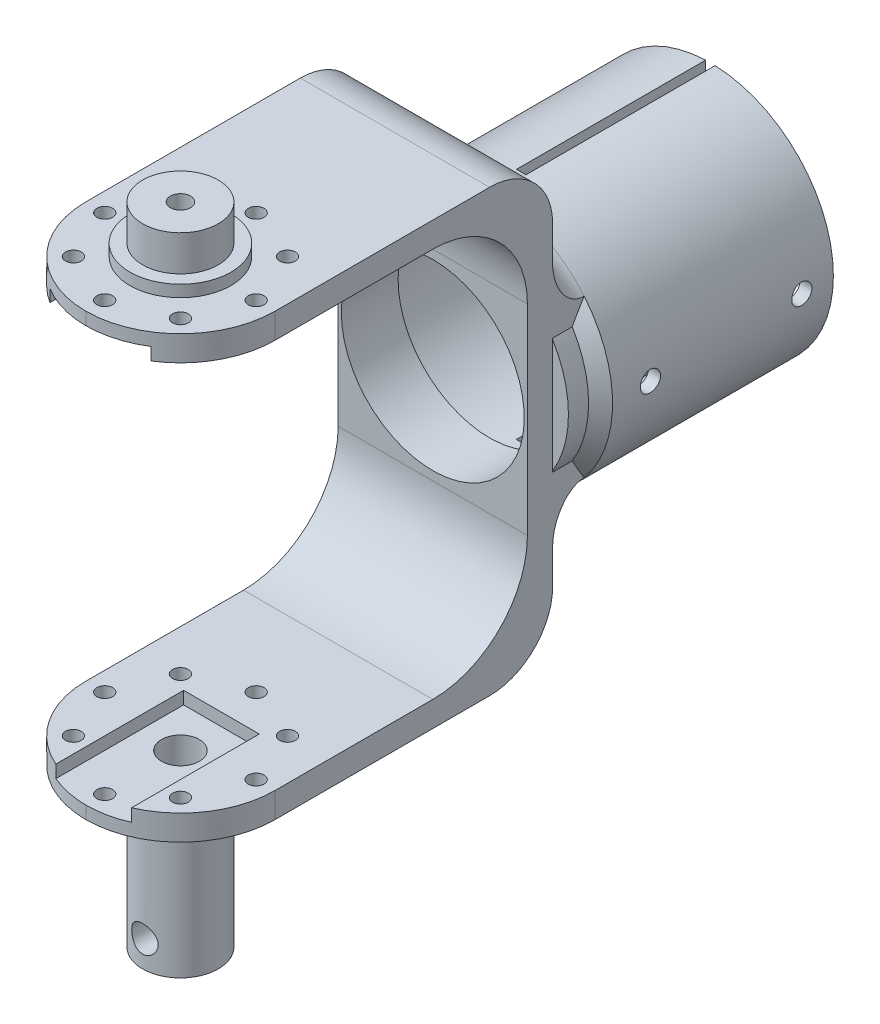
SolidWorks part; units mm, degrees
ref_plane "前视基准面" through (0, 0, 0) normal (0, 0, 1) x (1, 0, 0)
ref_plane "上视基准面" through (0, 0, 0) normal (0, 1, 0) x (1, 0, 0)
ref_plane "右视基准面" through (0, 0, 0) normal (1, 0, 0) x (0, 0, -1)
sketch "草图1" plane through (0, 0, 0) normal (1, 0, 0) x (0, 0, -1)
  line L0 (-27.5, 34.9) -> (31.5, 34.9)
  line L1 (-27.5, 30.9) -> (27.5, 30.9)
  line L2 (31.5, 34.9) -> (31.5, -34.9)
  line L3 (-27.5, -30.9) -> (27.5, -30.9)
  line L4 (27.5, 30.9) -> (27.5, -30.9)
  line L5 (-27.5, 30.9) -> (27.5, -30.9) construction
  line L6 (-27.5, -30.9) -> (27.5, 30.9) construction
  line L7 (-27.5, -34.9) -> (31.5, -34.9)
  line L8 (-27.5, 34.9) -> (-27.5, 30.9)
  line L9 (-27.5, -30.9) -> (-27.5, -34.9)
  point P0 (0, 0)
  dimension "D1" = 61.8
  dimension "D2" = 55
  dimension "D4" = 55
  dimension "D3" = 4
extrude "凸台-拉伸1" add sketch "草图1" along normal blind 30
sketch "草图4" plane through (0, 34.9, 0) normal (0, 1, 0) x (1, 0, 0)
  line L0 (30, 31.5) -> (30, -27.5) construction
  line L1 (30, -27.5) -> (0, -27.5) construction
  circle A0 centre (15, -12.5) radius 12 construction
  circle A1 centre (15, -0.5) radius 1.25
  circle A2 centre (15, -12.5) radius 12 construction
  circle A3 centre (23.4853, -4.0147) radius 1.25
  circle A4 centre (15, -12.5) radius 12 construction
  circle A5 centre (27, -12.5) radius 1.25
  circle A6 centre (15, -12.5) radius 12 construction
  circle A7 centre (23.4853, -20.9853) radius 1.25
  circle A8 centre (15, -12.5) radius 12 construction
  circle A9 centre (15, -24.5) radius 1.25
  circle A10 centre (15, -12.5) radius 12 construction
  circle A11 centre (6.5147, -20.9853) radius 1.25
  circle A12 centre (15, -12.5) radius 12 construction
  circle A13 centre (3, -12.5) radius 1.25
  circle A14 centre (15, -12.5) radius 12 construction
  circle A15 centre (6.5147, -4.0147) radius 1.25
  circle A16 centre (15, -12.5) radius 1.6
  point P31 (15, -12.5)
  dimension "D2" = 15
  dimension "D3" = 24
  dimension "D4" = 2.5
  dimension "D6" = 3.2
  dimension "D1" = 15
  dimension "D5" = 8
extrude "切除-拉伸1" cut sketch "草图4" against normal through all
fillet "圆角1" radius 15 6 edges at (0, 32.9, 27.5) (30, 32.9, 27.5) (30, -32.9, 27.5) (0, -32.9, 27.5) (15, -30.9, -27.5) (15, 30.9, -27.5)
fillet "圆角2" radius 10 2 edges at (15, -34.9, -31.5) (15, 34.9, -31.5)
sketch "草图5" plane through (0, 0, -31.5) normal (0, 0, -1) x (-1, 0, 0)
  line L0 (-30, -24.9) -> (-30, 24.9) construction
  circle A0 centre (-15, 0) radius 17.6
  circle A1 centre (-15, 0) radius 19.5
  dimension "D2" = 35.2
  dimension "D3" = 39
  dimension "D1" = 15
extrude "凸台-拉伸2" add sketch "草图5" along normal blind 40
sketch "草图7" plane through (0, 0, -71.5) normal (0, 0, -1) x (-1, 0, 0)
  line L1 (-15.75, 42.3131) -> (-14.25, 42.3131)
  line L2 (-15.75, 42.3131) -> (-15.75, -42.3131)
  line L3 (-15.75, -42.3131) -> (-14.25, -42.3131)
  line L4 (-14.25, 42.3131) -> (-14.25, -42.3131)
  line L5 (-15.75, 42.3131) -> (-14.25, -42.3131) construction
  line L6 (-15.75, -42.3131) -> (-14.25, 42.3131) construction
  point P0 (-15, 0)
  dimension "D1" = 1.5
extrude "切除-拉伸3" cut sketch "草图7" against normal blind 30
sketch "草图8" plane through (0, 0, 0) normal (1, 0, 0) x (0, 0, -1)
  line L0 (-977.5, 0) -> (49022.5, 0) construction
  line L1 (27.5, 15.9) -> (27.5, -15.9) construction
  line L2 (71.5, -19.4856) -> (71.5, 19.4856) construction
  line L3 (27.5, 15.9) -> (27.5, -15.9) construction
  circle A0 centre (66.5, 0) radius 1.6
  circle A1 centre (42.5, 0) radius 1.6
  point P5 (27.5, 0)
  dimension "D1" = 3.2
  dimension "D2" = 15
  dimension "D3" = 5
  dimension "D4" = 3.2
extrude "切除-拉伸4" cut sketch "草图8" along normal through all and the other way blind 8
sketch "草图10" plane through (0, 0, -31.5) normal (0, 0, -1) x (-1, 0, 0)
  circle A0 centre (-15, 0) radius 17.5
extrude "凸台-拉伸4" add sketch "草图10" along normal blind 5
chamfer "倒角2" distance 5 angle 45 2 edges at (34.5, 0, -31.5) (-4.5, 0, -31.5)
sketch "草图11" plane through (0, -34.9, 0) normal (0, -1, 0) x (1, 0, 0)
  circle A0 centre (15, 12.5) radius 8
  circle A1 centre (15, 12.5) radius 3
  dimension "D1" = 16
  dimension "D2" = 6
extrude "凸台-拉伸5" add sketch "草图11" along normal blind 25
sketch "草图12" plane through (0, -59.9, 0) normal (0, -1, 0) x (1, 0, 0)
  circle A0 centre (15, 12.5) radius 6
  dimension "D1" = 12
extrude "切除-拉伸5" cut sketch "草图12" against normal blind 23.15 flip side to cut
sketch "草图15" plane through (0, 34.9, 0) normal (0, 1, 0) x (1, 0, 0)
  circle A0 centre (15, -12.5) radius 8
  circle A1 centre (15, -12.5) radius 1.6
  dimension "D1" = 16
  dimension "D2" = 3.2
extrude "凸台-拉伸6" add sketch "草图15" along normal blind 7.5
sketch "草图16" plane through (0, 42.4, 0) normal (0, 1, 0) x (1, 0, 0)
  circle A0 centre (15, -12.5) radius 6
  dimension "D1" = 12
extrude "切除-拉伸6" cut sketch "草图16" against normal blind 5.65 flip side to cut
fillet "圆角3" radius 5 2 edges at (15, 19.5, -31.5) (15, -19.5, -31.5)
sketch "草图17" plane through (0, -34.9, 0) normal (0, -1, 0) x (1, 0, 0)
  circle A0 centre (15, 12.5) radius 3 construction
  circle A1 centre (15, 12.5) radius 3
extrude "切除-拉伸7" cut sketch "草图17" against normal blind 8
ref_plane "基准面1" through (0, 0, 12.5) normal (0, 0, -1) x (-1, 0, 0)
sketch "草图19" plane through (0, 0, 12.5) normal (0, 0, -1) x (-1, 0, 0)
  line L0 (0, 30.9) -> (-30, 30.9) construction
  line L1 (-7, 32.9) -> (-23, 32.9)
  line L2 (-7, 32.9) -> (-7, 28.9)
  line L3 (-7, 28.9) -> (-23, 28.9)
  line L4 (-23, 32.9) -> (-23, 28.9)
  line L5 (-7, 32.9) -> (-23, 28.9) construction
  line L6 (-7, 28.9) -> (-23, 32.9) construction
  line L7 (-30, -30.9) -> (0, -30.9) construction
  line L8 (-9, -32.9) -> (-21, -32.9)
  line L9 (-9, -32.9) -> (-9, -28.9)
  line L10 (-9, -28.9) -> (-21, -28.9)
  line L11 (-21, -32.9) -> (-21, -28.9)
  line L12 (-9, -32.9) -> (-21, -28.9) construction
  line L13 (-9, -28.9) -> (-21, -32.9) construction
  point P0 (-15, 30.9)
  point P7 (-15, -30.9)
  dimension "D1" = 12
  dimension "D2" = 4
  dimension "D3" = 16
  dimension "D4" = 4
extrude "切除-拉伸8" cut sketch "草图19" against normal blind 20 and the other way blind 6.5
sketch "草图20" plane through (0, 0, -36.5) normal (0, 0, -1) x (-1, 0, 0)
  circle A2 centre (-15, 0) radius 14.5
  circle A3 centre (-15, 0) radius 14.5
  dimension "D1" = 3
extrude "切除-拉伸9" cut sketch "草图20" against normal blind 20
ref_axis "基准轴1" through (15, -59.9, 12.5) along (0, 1, 0)
ref_plane "基准面2" through (1.25, 0, -1.25) normal (-0.7071, 0, 0.7071) x (0, 1, 0)
ref_plane "基准面3" through (0, -51.75, 0) normal (0, -1, 0) x (-1, 0, 0)
sketch "草图21" plane through (0, -51.75, 0) normal (0, -1, 0) x (-1, 0, 0)
  line L0 (-15, -12.5) -> (-15, 15.533)
  line L1 (-15, -12.5) -> (-33.3603, 9.381)
  dimension "D1" = 40
ref_plane "基准面4" through (33.3603, -51.75, -9.381) normal (0.6428, 0, -0.766) x (-0.766, 0, -0.6428)
sketch "草图22" plane through (33.3603, -51.75, -9.381) normal (0.6428, 0, -0.766) x (-0.766, 0, -0.6428)
  circle A0 centre (0, 0) radius 2
  dimension "D1" = 4
extrude "切除-拉伸10" [suppressed] cut sketch "草图22" against normal through all
ref_plane "基准面5" through (0, -55.75, 0) normal (0, -1, 0) x (-1, 0, 0)
sketch "草图23" plane through (0, -55.75, 0) normal (0, -1, 0) x (-1, 0, 0)
  line L0 (-15, -12.5) -> (-15, 15.533) construction
  line L1 (-15, -12.5) -> (-15, 15.533)
ref_plane "基准面6" through (15, -55.75, -15.533) normal (0, 0, -1) x (-1, 0, 0)
sketch "草图24" plane through (15, -55.75, -15.533) normal (0, 0, -1) x (-1, 0, 0)
  circle A0 centre (0, 0) radius 2.1
  dimension "D1" = 4.2
extrude "切除-拉伸11" cut sketch "草图24" against normal through all
